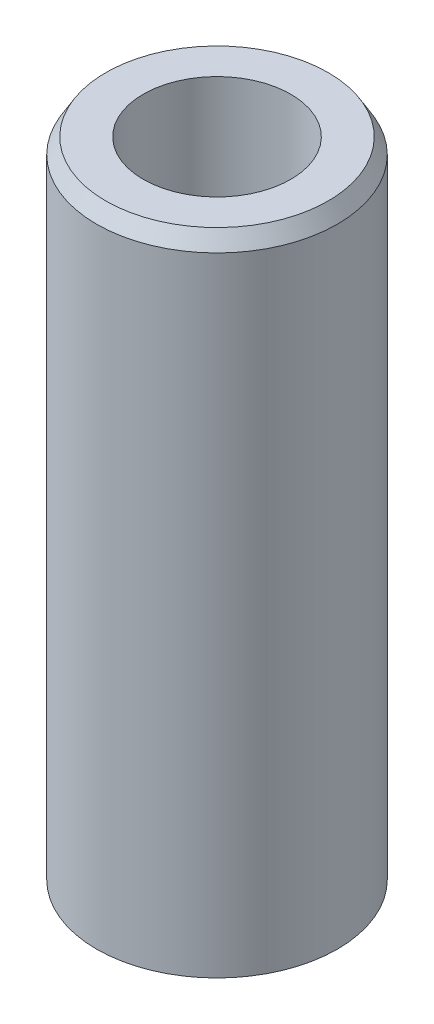
SolidWorks part; units mm, degrees
ref_plane "Front Plane" through (0, 0, 0) normal (0, 0, 1) x (1, 0, 0)
ref_plane "Top Plane" through (0, 0, 0) normal (0, 1, 0) x (1, 0, 0)
ref_plane "Right Plane" through (0, 0, 0) normal (1, 0, 0) x (0, 0, -1)
sketch "Sketch1" plane through (0, 0, 0) normal (0, 1, 0) x (1, 0, 0)
  circle A0 centre (0, 0) radius 20
  dimension "SHAFT_OD" = 40
extrude "Boss-Extrude1" add sketch "Sketch1" along normal blind 108.3877
sketch "Sketch2" plane through (0, 0, 0) normal (0, 1, 0) x (1, 0, 0)
  circle A0 centre (0, 0) radius 12.2555
  dimension "BORE_D" = 24.5111
extrude "Cut-Extrude1" cut sketch "Sketch2" along normal through all
chamfer "Chamfer1" distance 2.575 angle 30.709 2 edges at (0, 108.3877, 20) (0, 0, 20) first distance on face at (0, 108.3877, 20) first distance on face at (0, 0, 12.2555)
